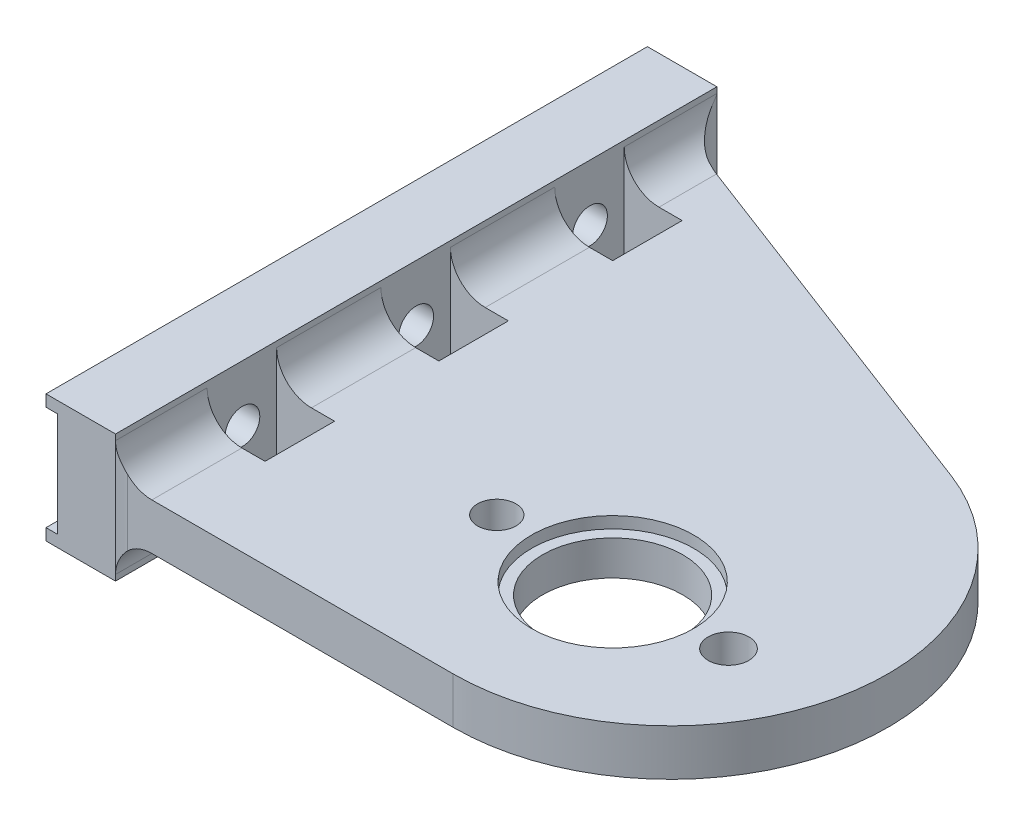
SolidWorks part; units mm, degrees
ref_plane "前视基准面" through (0, 0, 0) normal (0, 0, 1) x (1, 0, 0)
ref_plane "上视基准面" through (0, 0, 0) normal (0, 1, 0) x (1, 0, 0)
ref_plane "右视基准面" through (0, 0, 0) normal (1, 0, 0) x (0, 0, -1)
ref_plane "基准面4" through (0, 0, 0) normal (0, -1, 0) x (1, 0, 0)
sketch "草图1" plane through (0, 0, 0) normal (0, -1, 0) x (1, 0, 0)
  line L0 (-29, 18.9063) -> (-29, -33)
  line L1 (-27.0707, -30.3664) -> (6.6677, -17.5436)
  line L2 (0, 18.768) -> (-28.0994, 18.768)
  arc A0 (-28.0994, 18.768) -> (-29, 18.9063) centre (-28.0994, 21.768) cw
  arc A1 (-29, -33) -> (-27.0707, -30.3664) centre (-26.0049, -33.1707) cw
  arc A2 (6.6677, -17.5436) -> (0, 18.768) centre (0, 0) ccw
  point P9 (0, 0)
extrude "凸台-拉伸1" add sketch "草图1" against normal blind 4
sketch "草图2" plane through (0, 4, 0) normal (0, 1, 0) x (-1, 0, 0)
  line L0 (29, 18.768) -> (29, -20.0778)
  line L1 (29, -20.0778) -> (0, -20.0778)
  line L2 (0, -20.0778) -> (0, 18.768)
  line L3 (0, 18.768) -> (29, 18.768)
extrude "凸台-拉伸2" add sketch "草图2" along normal blind 3.5
sketch "草图3" plane through (0, 0, 18.768) normal (0, 0, 1) x (1, 0, 0)
  line L0 (-29, 4) -> (-29, 7.5)
  line L1 (-29, 7.5) -> (0, 7.5)
  line L2 (0, 7.5) -> (0, 4)
  line L3 (0, 4) -> (-29, 4)
extrude "凸台-拉伸3" add sketch "草图3" along normal blind 0.1384
sketch "草图4" plane through (0, 0, -20.0778) normal (0, 0, -1) x (-1, 0, 0)
  line L0 (29, 7.5) -> (29, 4)
  line L1 (29, 4) -> (0, 4)
  line L2 (0, 4) -> (0, 7.5)
  line L3 (0, 7.5) -> (29, 7.5)
extrude "凸台-拉伸4" add sketch "草图4" along normal blind 12.9222
sketch "草图5" plane through (-29, 0, 0) normal (-1, 0, 0) x (0, 0, 1)
  line L0 (18.9063, 0) -> (-33, 0)
  line L1 (-33, 0) -> (-33, 7.5)
  line L2 (-33, 7.5) -> (18.9063, 7.5)
  line L3 (18.9063, 7.5) -> (18.9063, 0)
extrude "凸台-拉伸5" add sketch "草图5" along normal blind 6
sketch "草图6" plane through (0, 0, 0) normal (1, 0, 0) x (0, 0, -1)
  line L0 (-18.9063, 4) -> (-18.768, 4)
  line L1 (-18.768, 4) -> (31.0229, 4)
  line L2 (31.0229, 4) -> (33, 4)
  line L3 (33, 4) -> (33, 7.5)
  line L4 (33, 7.5) -> (-18.9063, 7.5)
  line L5 (-18.9063, 7.5) -> (-18.9063, 4)
extrude "切除-拉伸1" cut sketch "草图6" against normal blind 28.0994
sketch "草图7" plane through (-28.0994, 0, 0) normal (1, 0, 0) x (0, 0, -1)
  line L0 (-18.9063, 4) -> (33, 4)
  line L1 (33, 4) -> (33, 7.5)
  line L2 (33, 7.5) -> (-18.9063, 7.5)
  line L3 (-18.9063, 7.5) -> (-18.9063, 4)
extrude "切除-拉伸2" cut sketch "草图7" against normal blind 0.9006
ref_plane "基准面6" through (0, 0, 11) normal (0, 0, 1) x (1, 0, 0)
sketch "草图9" plane through (0, 0, 11) normal (0, 0, 1) x (1, 0, 0)
  line L0 (-29, 4) -> (-29, 0)
  line L1 (-29, 0) -> (-24, 0)
  line L2 (-24, 0) -> (-24, 4)
  line L3 (-24, 4) -> (-29, 4)
extrude "切除-拉伸4" cut sketch "草图9" against normal blind 6
ref_plane "基准面7" through (0, 0, -4) normal (0, 0, 1) x (1, 0, 0)
sketch "草图10" plane through (0, 0, -4) normal (0, 0, 1) x (1, 0, 0)
  line L0 (-29, 4) -> (-29, 0)
  line L1 (-29, 0) -> (-24, 0)
  line L2 (-24, 0) -> (-24, 4)
  line L3 (-24, 4) -> (-29, 4)
extrude "切除-拉伸5" cut sketch "草图10" against normal blind 6
sketch "草图11" plane through (0, 0, 0) normal (0, -1, 0) x (1, 0, 0)
  line L0 (-29, -33) -> (-35, -33)
  line L1 (-35, -33) -> (-35, 18.9063)
  line L2 (-35, 18.9063) -> (-29, 18.9063)
  line L3 (-29, 18.9063) -> (-29, -33)
extrude "凸台-拉伸6" add sketch "草图11" along normal blind 3.5
sketch "草图12" plane through (0, 0, 18.9063) normal (0, 0, 1) x (1, 0, 0)
  line L0 (-35, 6.5) -> (-35, -2.5)
  line L1 (-35, -2.5) -> (-34, -2.5)
  line L2 (-34, -2.5) -> (-34, 6.5)
  line L3 (-34, 6.5) -> (-35, 6.5)
extrude "切除-拉伸6" cut sketch "草图12" against normal through all
hole_wizard "Ø8.0 (8) 直径孔1" positions "草图18" profile "草图17" hole size "Ø8.0" standard "ANSI Metric"
sketch "草图18" plane through (0, 0, 0) normal (0, -1, 0) x (-1, 0, 0)
  point P0 (0, -5)
  dimension "D1" = 5
sketch "草图17" plane through (0, 0, 5) normal (1, 0, 0) x (0, 0, -1)
  line L0 (0, 0) -> (0, 7.5)
  line L1 (0, 7.5) -> (6.05, 7.5)
  line L2 (6.05, 7.5) -> (6.05, 0)
  line L5 (6.05, 0) -> (0, 0)
  line L11 (0, -6.35) -> (0, 107.95) construction
  dimension "通孔孔直径" = 12.1
  dimension "通孔孔深度" = 7.5
fillet "圆角1" radius 3 6 edges tangent propagation no
sketch "草图22" plane through (0, 4, 0) normal (0, 1, 0) x (1, 0, 0)
  line L0 (0, 0) -> (0, 12.2) construction
  line L1 (0, 0) -> (0, -12.3) construction
  circle A0 centre (-10, -5) radius 1.6591
  circle A1 centre (10, -5) radius 1.7615
  circle A2 centre (0, -5) radius 6.05 construction
  dimension "D1" = 10
  dimension "D2" = 10
extrude "切除-拉伸7" cut sketch "草图22" against normal blind 10
sketch "草图24" plane through (-34, 0, 0) normal (-1, 0, 0) x (0, 0, 1)
  line L0 (-33, -2.5) -> (-33, 6.5) construction
  line L1 (18.9063, -2.5) -> (18.9063, 6.5) construction
  line L2 (-33, 2.5915) -> (18.9063, 2.5915) construction
  line L4 (-7.0468, 5.7753) -> (-7.0468, -1.7604) construction
  circle A0 centre (-7.0468, 2.5915) radius 1.5
  circle A1 centre (-22.0468, 2.5915) radius 1.5
  circle A2 centre (7.9532, 2.5915) radius 1.5
  dimension "D3" = 3
  dimension "D4" = 3
  dimension "D5" = 3
  dimension "D1" = 15
  dimension "D2" = 15
extrude "切除-拉伸8" cut sketch "草图24" against normal blind 10
ref_plane "基准面8" through (0, 0, -25) normal (0, 0, 1) x (1, 0, 0)
sketch "草图29" plane through (0, 0, -25) normal (0, 0, 1) x (1, 0, 0)
  line L0 (-24, 0) -> (-24, 7.5)
  line L2 (-24, 7.5) -> (-29, 7.5)
  line L3 (-26, 0) -> (6.6677, 0) construction
  line L5 (-29, 7.5) -> (-29, -3.5)
  line L6 (-29, -3.5) -> (-29, -3) construction
  line L7 (-29, -3.5) -> (-24, -3.5)
  line L8 (-24, -3.5) -> (-24, 0)
extrude "切除-拉伸10" cut sketch "草图29" along normal blind 5
extrude "切除-拉伸11" cut sketch "草图29<2>" along normal blind 6
sketch "草图29<2>" plane through (0, 0, -25) normal (0, 0, 1) x (1, 0, 0) same geometry as "草图29"
sketch "草图30" plane through (0, 4, 0) normal (0, 1, 0) x (1, 0, 0)
  circle A0 centre (0, -5) radius 7
  dimension "D1" = 14
extrude "切除-拉伸12" cut sketch "草图30" against normal blind 1
